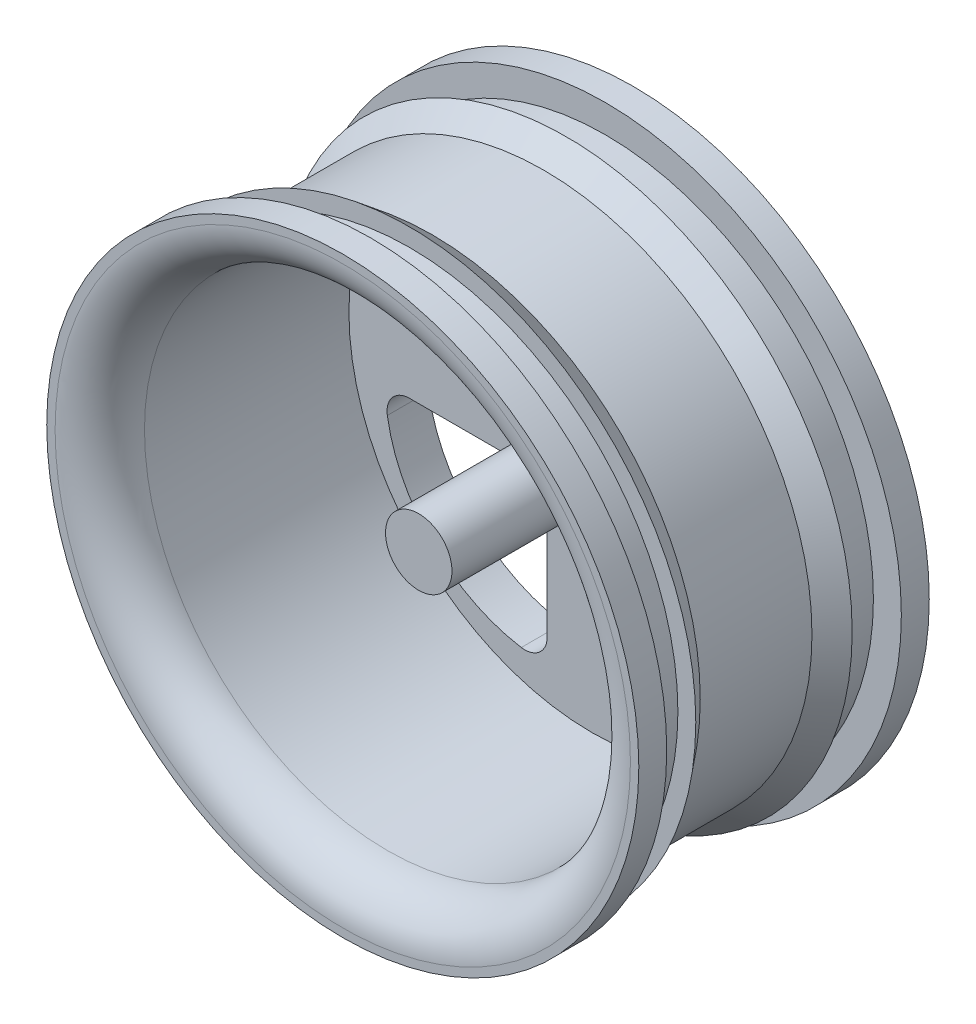
SolidWorks part; units mm, degrees
material "三聚氰胺甲醛树脂"
ref_plane "前视基准面" through (0, 0, 0) normal (0, 0, 1) x (1, 0, 0)
ref_plane "上视基准面" through (0, 0, 0) normal (0, 1, 0) x (1, 0, 0)
ref_plane "右视基准面" through (0, 0, 0) normal (1, 0, 0) x (0, 0, -1)
sketch "草图1" plane through (0, 0, 0) normal (1, 0, 0) x (0, 0, -1)
  line L0 (0, 0) -> (0, 24) construction
  line L1 (-5, 24) -> (5, 24)
  line L2 (5, 24) -> (7, 25.6)
  line L3 (7, 25.6) -> (7, 24)
  line L4 (7, 24) -> (10.5, 24)
  line L5 (10.5, 24) -> (10.5, 26.5)
  line L6 (10.5, 26.5) -> (13, 26.5)
  line L7 (13, 26.5) -> (13, 0)
  line L8 (13, 0) -> (-13, 0)
  line L9 (-13, 26.5) -> (-13, 0)
  line L10 (-10.5, 26.5) -> (-13, 26.5)
  line L11 (-10.5, 24) -> (-10.5, 26.5)
  line L12 (-7, 24) -> (-10.5, 24)
  line L13 (-7, 25.6) -> (-7, 24)
  line L14 (-5, 24) -> (-7, 25.6)
  dimension "D1" = 24
  dimension "D2" = 5
  dimension "D3" = 1.6
  dimension "D4" = 26
  dimension "D5" = 3.5
  dimension "D6" = 2.5
  dimension "D7" = 2.5
revolve "旋转1" add sketch "草图1" angle 360 about L8
sketch "草图3" plane through (0, 0, 13) normal (0, 0, 1) x (1, 0, 0)
  circle A0 centre (0, 0) radius 21.75
  dimension "D1" = 43.5
extrude "切除-拉伸1" cut sketch "草图3" against normal blind 22.3
fillet "圆角1" radius 4 1 edges at (21.75, 0, 13)
sketch "草图4" plane through (0, 0, -9.3) normal (0, 0, 1) x (1, 0, 0)
  line L0 (0, 0) -> (9.9974, 0) construction
  line L1 (0, 0) -> (8, 0)
  line L2 (0, 0) -> (0, 16.6399) construction
  line L3 (-4, 4) -> (-18.5, 4)
  line L4 (4, 4) -> (18.5, 4)
  line L5 (4, 4) -> (4, 18.5)
  line L6 (-4, 4) -> (-4, 18.5)
  line L7 (4, -4) -> (4, -18.5)
  line L8 (4, -4) -> (18.5, -4)
  line L9 (-4, -4) -> (-18.5, -4)
  line L10 (-4, -4) -> (-4, -18.5)
  circle A0 centre (0, 0) radius 2.975
  circle A1 centre (8, 0) radius 1.35
  circle A2 centre (0, -8) radius 1.35
  circle A3 centre (-8, 0) radius 1.35
  circle A4 centre (0, 8) radius 1.35
  arc A9 (18.5, 4) -> (4, 18.5) centre (4, 4) ccw
  arc A10 (-18.5, 4) -> (-4, 18.5) centre (-4, 4) cw
  arc A11 (18.5, -4) -> (4, -18.5) centre (4, -4) cw
  arc A12 (-18.5, -4) -> (-4, -18.5) centre (-4, -4) ccw
  point P16 (0, 0)
  dimension "D1" = 5.95
  dimension "D2" = 2.7
  dimension "D6" = 14.5
  dimension "D3" = 8
  dimension "D4" = 4
ref_axis "基准轴1" through (0, 0, 0) along (0, 0, 1)
extrude "切除-拉伸3" cut sketch "草图4" against normal up to next contours A10 L3 L6 | L4 A9 L5 | A11 L8 L7 | L9 A12 L10 | A3 | A4 | A1 | A2 region at (8, 1.3118, -9.3) region at (-10.154, 10.154, -9.3) region at (10.154, 10.154, -9.3) region at (10.154, -10.154, -9.3) region at (-10.154, -10.154, -9.3) region at (0, -8, -9.3) region at (-8, 0, -9.3) region at (0, 8, -9.3)
sketch "草图6" plane through (0, 0, -9.3) normal (0, 0, 1) x (1, 0, 0)
  circle A0 centre (0, 0) radius 2.975
  dimension "D1" = 5.95
extrude "凸台-拉伸2" add sketch "草图6" along normal blind 15.5 contours A0 region at (0, 0, -9.3)
fillet "圆角2" radius 2 12 edges at (18.5, -4, -11.15) (4, -18.5, -11.15) (4, -4, -11.15) (4, 18.5, -11.15) (18.5, 4, -11.15) (4, 4, -11.15) (-4, 18.5, -11.15) (-4, 4, -11.15) (-18.5, 4, -11.15) (-4, -4, -11.15) (-18.5, -4, -11.15) (-4, -18.5, -11.15)
